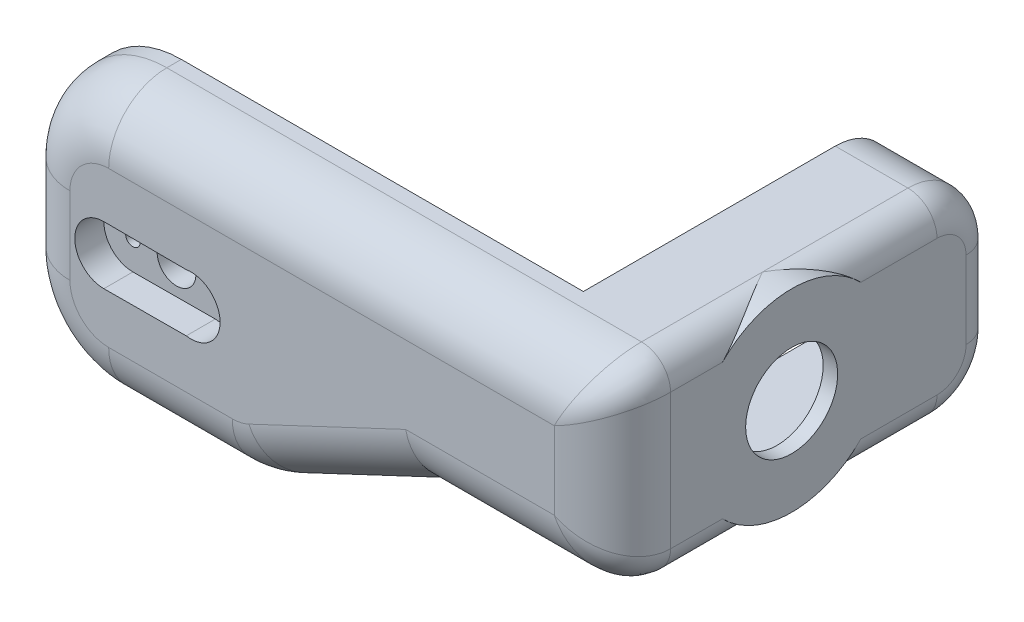
SolidWorks part; units mm, degrees
ref_plane "Front Plane" through (0, 0, 0) normal (0, 0, 1) x (1, 0, 0)
ref_plane "Top Plane" through (0, 0, 0) normal (0, 1, 0) x (1, 0, 0)
ref_plane "Right Plane" through (0, 0, 0) normal (1, 0, 0) x (0, 0, -1)
sketch "Sketch1" plane through (0, 0, 0) normal (0, 0, 1) x (1, 0, 0)
  line L0 (0, 0) -> (0, 28)
  line L1 (0, 28) -> (62, 28)
  line L2 (62, 28) -> (62, 8)
  line L4 (25, 0) -> (0, 0)
  line L5 (62, 8) -> (42, 8)
  line L6 (42, 8) -> (25, 0)
  dimension "D1" = 28
  dimension "D2" = 62
  dimension "D3" = 25
  dimension "D4" = 20
  dimension "D5" = 20
extrude "Boss-Extrude1" add sketch "Sketch1" along normal blind 7.5
sketch "Sketch2" plane through (0, 0, 7.5) normal (0, 0, 1) x (1, 0, 0)
  circle A0 centre (14, 14) radius 2
  circle A1 centre (18.5, 14) radius 0.75
  circle A2 centre (9.5, 14) radius 0.75
  dimension "D3" = 4
  dimension "D6" = 1.5
  dimension "D7" = 1.5
  dimension "D1" = 14
  dimension "D2" = 14
  dimension "D4" = 4.5
  dimension "D5" = 4.5
extrude "Cut-Extrude1" cut sketch "Sketch2" against normal blind 8.5
sketch "Sketch3" plane through (0, 0, 7.5) normal (0, 0, 1) x (1, 0, 0)
  line L0 (9.5, 17) -> (18.0068, 16.9592)
  line L1 (9.5, 11) -> (18.0068, 11.0408)
  arc A0 (9.5, 17) -> (9.5, 11) centre (9.5, 14) ccw
  arc A1 (18.0068, 11.0408) -> (18.0068, 16.9592) centre (18.5, 14) ccw
  dimension "D1" = 6
  dimension "D2" = 6
extrude "Cut-Extrude2" cut sketch "Sketch3" against normal blind 3
sketch "Sketch4" plane through (0, 0, 0) normal (0, 0, -1) x (-1, 0, 0)
  line L0 (-62, 28) -> (0, 28) construction
  line L1 (-62, 8) -> (-51.5, 8)
  line L2 (-62, 8) -> (-62, 28)
  line L3 (-62, 28) -> (-51.5, 28)
  line L4 (-51.5, 8) -> (-51.5, 28)
  dimension "D1" = 10.5
  dimension "D2" = 0
  dimension "D3" = 20
extrude "Boss-Extrude2" add sketch "Sketch4" along normal blind 32
fillet "Fillet1" radius 10 3 edges at (0, 0, 3.75) (0, 28, 3.75) (25, 0, 3.75)
fillet "Fillet2" radius 6 11 edges at (56.75, 8, -32) (56.75, 28, -32) (36, 28, 7.5) (2.9289, 25.0711, 7.5) (0, 14, 7.5) (2.9289, 2.9289, 7.5) (16.3823, 0, 7.5) (24.9462, 0.2409, 7.5) (34.5113, 4.4759, 7.5) (52, 8, 7.5) (62, 18, 7.5)
fillet "Fillet5" radius 3 7 edges at (60.2426, 26.2426, 5.7426) (60.2426, 9.7574, 5.7426) (62, 8, -12.25) (62, 9.7574, -30.2426) (62, 18, -32) (62, 26.2426, -30.2426) (62, 28, -12.25)
sketch "Sketch10" plane through (51.5, 0, 0) normal (-1, 0, 0) x (0, 0, 1)
  circle A0 centre (-11, 18) radius 10
  dimension "D3" = 20
  dimension "D1" = 18
  dimension "D2" = 11
extrude "Boss-Extrude4" add sketch "Sketch10" against normal blind 10.5
sketch "Sketch5" plane through (51.5, 0, 0) normal (-1, 0, 0) x (0, 0, 1)
  circle A0 centre (-11, 18) radius 4.75
  dimension "D3" = 9.5
  dimension "D1" = 18
  dimension "D2" = 11
extrude "Cut-Extrude3" cut sketch "Sketch5" against normal blind 30
sketch "Sketch7" plane through (51.5, 0, 0) normal (-1, 0, 0) x (0, 0, 1)
  line L1 (-27.3, 12) -> (-5, 12)
  line L2 (-27.3, 12) -> (-27.3, 24.6)
  line L3 (-27.3, 24.6) -> (-5, 24.6)
  line L4 (-5, 12) -> (-5, 24.6)
  dimension "D1" = 22.3
  dimension "D2" = 12.6
  dimension "D3" = 12
  dimension "D4" = 5
extrude "Cut-Extrude4" cut sketch "Sketch7" against normal blind 9
sketch "Sketch8" plane through (51.5, 0, 0) normal (-1, 0, 0) x (0, 0, 1)
  circle A0 centre (-29.5, 18) radius 0.7719
  circle A1 centre (-2.5, 18) radius 0.7682
  dimension "D1" = 2.5
  dimension "D2" = 27
  dimension "D3" = 18
extrude "Cut-Extrude5" cut sketch "Sketch8" against normal blind 9
